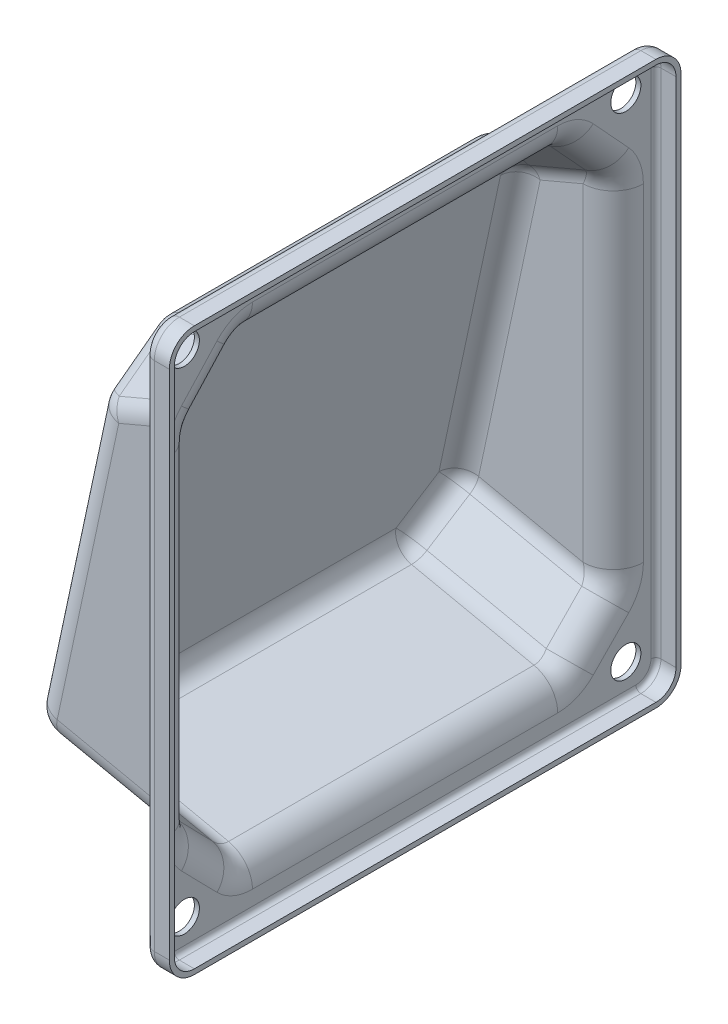
SolidWorks part; units mm, degrees
material "Q235"
ref_plane "前视基准面" through (0, 0, 0) normal (0, 0, 1) x (1, 0, 0)
ref_plane "上视基准面" through (0, 0, 0) normal (0, 1, 0) x (1, 0, 0)
ref_plane "右视基准面" through (0, 0, 0) normal (1, 0, 0) x (0, 0, -1)
sketch "草图1" plane through (0, 0, 0) normal (0, 0, 1) x (1, 0, 0)
  line L0 (0, 0) -> (0, 56)
  line L1 (0, 0) -> (0, -56)
  line L2 (0, 56) -> (-5, 56)
  line L3 (-5, 56) -> (-5, -56)
  line L4 (-5, -56) -> (0, -56)
extrude "拉伸1" add sketch "草图1" along normal mid plane 102
sketch "草图2" plane through (0, 0, 0) normal (0, 0, 1) x (1, 0, 0)
  line L1 (-5, 56) -> (-5, -56) construction
  line L2 (-5, 47) -> (-21.1088, 40.1622)
  line L4 (-5, -47) -> (-38.257, -39.931)
  line L5 (-38.257, -39.931) -> (-21.1088, 40.1622)
  line L6 (-5, 47) -> (-5, -47)
  dimension "D3" = 34
  dimension "D4" = 17.5
extrude "拉伸2" add sketch "草图2" along normal mid plane 85
chamfer "倒角1" distance 10 angle 45 4 edges at (-21.6285, -43.4655, -42.5) (-21.6285, -43.4655, 42.5) (-13.0544, 43.5811, 42.5) (-13.0544, 43.5811, -42.5)
fillet "圆角1" radius 5 4 edges at (-2.5, -56, -51) (-2.5, -56, 51) (-2.5, 56, -51) (-2.5, 56, 51)
fillet "圆角2" radius 5 8 edges at (-20.5817, -33.4646, -42.5) (-21.6285, -43.4655, -32.5) (-21.6285, -43.4655, 32.5) (-20.5817, -33.4646, 42.5) (-14.3336, 32.1745, 42.5) (-13.0544, 43.5811, 32.5) (-13.0544, 43.5811, -32.5) (-14.3336, 32.1745, -42.5)
fillet "圆角3" radius 5 32 edges at (-21.2062, 39.7074, 32.3423) (-22.3881, 34.1874, 37.5) (-23.7076, 28.0242, 42.1194) (-29.9635, -1.1948, 42.5) (-36.1304, -29.9984, 42.1194) (-37.2102, -35.0418, 37.5) (-38.1773, -39.5588, 32.3423) (-38.257, -39.931, 0) (-38.1773, -39.5588, -32.3423) (-37.2102, -35.0418, -37.5) (-36.1304, -29.9984, -42.1194) (-29.9635, -1.1948, -42.5) (-23.7076, 28.0242, -42.1194) (-22.3881, 34.1874, -37.5) (-21.2062, 39.7074, -32.3423) (-5, 46.5865, 32.3423) (-5, 41.5682, 37.5) (-5, 35.9651, 42.1194) (-5, -0.3864, 42.5) (-5, -36.6154, 42.1194) (-5, -41.8883, 37.5) (-5, -46.6109, 32.3423) (-5, -47, 0) (-5, -46.6109, -32.3423) (-5, -41.8883, -37.5) (-5, -36.6154, -42.1194) (-5, -0.3864, -42.5) (-5, 35.9651, -42.1194) (-5, 41.5682, -37.5) (-5, 46.5865, -32.3423) (-21.1088, 40.1622, 0) (-5, 47, 0)
fillet "圆角4" radius 2 8 edges at (-5, 54.5355, -49.5355) (-5, 56, 0) (-5, 54.5355, 49.5355) (-5, 0, 51) (-5, -54.5355, 49.5355) (-5, -56, 0) (-5, -54.5355, -49.5355) (-5, 0, -51)
shell "抽壳1" thickness 1 removed face at (0, 0, 0)
sketch "草图3" plane through (-4, 0, 0) normal (1, 0, 0) x (0, 0, -1)
  circle A0 centre (44, 49) radius 3
  circle A1 centre (-44, 49) radius 3
  circle A2 centre (44, -49) radius 3
  circle A3 centre (-44, -49) radius 3
extrude "拉伸3" cut sketch "草图3" against normal through all
scale "缩放比例1" scale about origin uniform scaling yes scale factor 0.25
